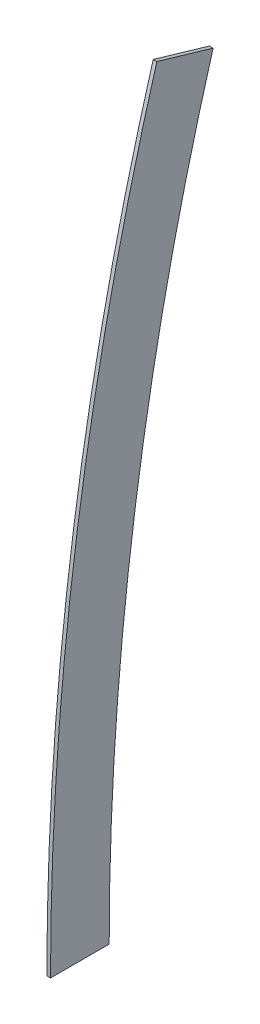
SolidWorks part; units mm, degrees
ref_plane "Front Plane" through (0, 0, 0) normal (0, 0, 1) x (1, 0, 0)
ref_plane "Top Plane" through (0, 0, 0) normal (0, 1, 0) x (1, 0, 0)
ref_plane "Right Plane" through (0, 0, 0) normal (1, 0, 0) x (0, 0, -1)
sketch "Sketch1" plane through (0, 0, 0) normal (1, 0, 0) x (0, 0, -1)
  line L0 (0, 0) -> (25.4, 0)
  line L1 (70.4116, 313.5292) -> (46.0375, 320.675)
  line L2 (1139.8524, 0) -> (46.0375, 320.675) construction
  arc A0 (25.4, 0) -> (70.4116, 313.5292) centre (1139.8524, 0) cw
  arc A1 (0, 0) -> (46.0375, 320.675) centre (1139.8524, 0) cw
  point P0 (0, 0)
  point P1 (46.0375, 320.675)
  dimension "D3" = 25.4
  dimension "D1" = 320.675
  dimension "D2" = 46.0375
base flange "Base-Flange1" sketch "Sketch1" thickness 1.5875 reverse thickness direction no parameters "D1"=3.175
sketch "Bend-Lines1" [suppressed] plane through (0, 0, 0) normal (0, 1, 0) x (1, 0, 0)
sketch "Bounding-Box1" [suppressed] plane through (0, 0, 0) normal (0, 1, 0) x (1, 0, 0)
sheet metal parameters "Sheet-Metal3" thickness 1.5875 parameters "D1"=3.175
flat pattern "Flat-Pattern3" [suppressed]
sketch "Bend-Lines2" plane through (0, 0, 0) normal (0, 1, 0) x (1, 0, 0)
sketch3d "Bounding-Box2" [suppressed]
  line L0 (1105.2655, 322.3189, 0) -> (1151.303, 1.6439, 0) construction
  line L1 (1068.9278, 317.1021, 0) -> (1114.9653, -3.5729, 0) construction
  line L2 (1105.2655, 322.3189, 0) -> (1068.9278, 317.1021, 0) construction
  line L3 (1151.303, 1.6439, 0) -> (1114.9653, -3.5729, 0) construction
